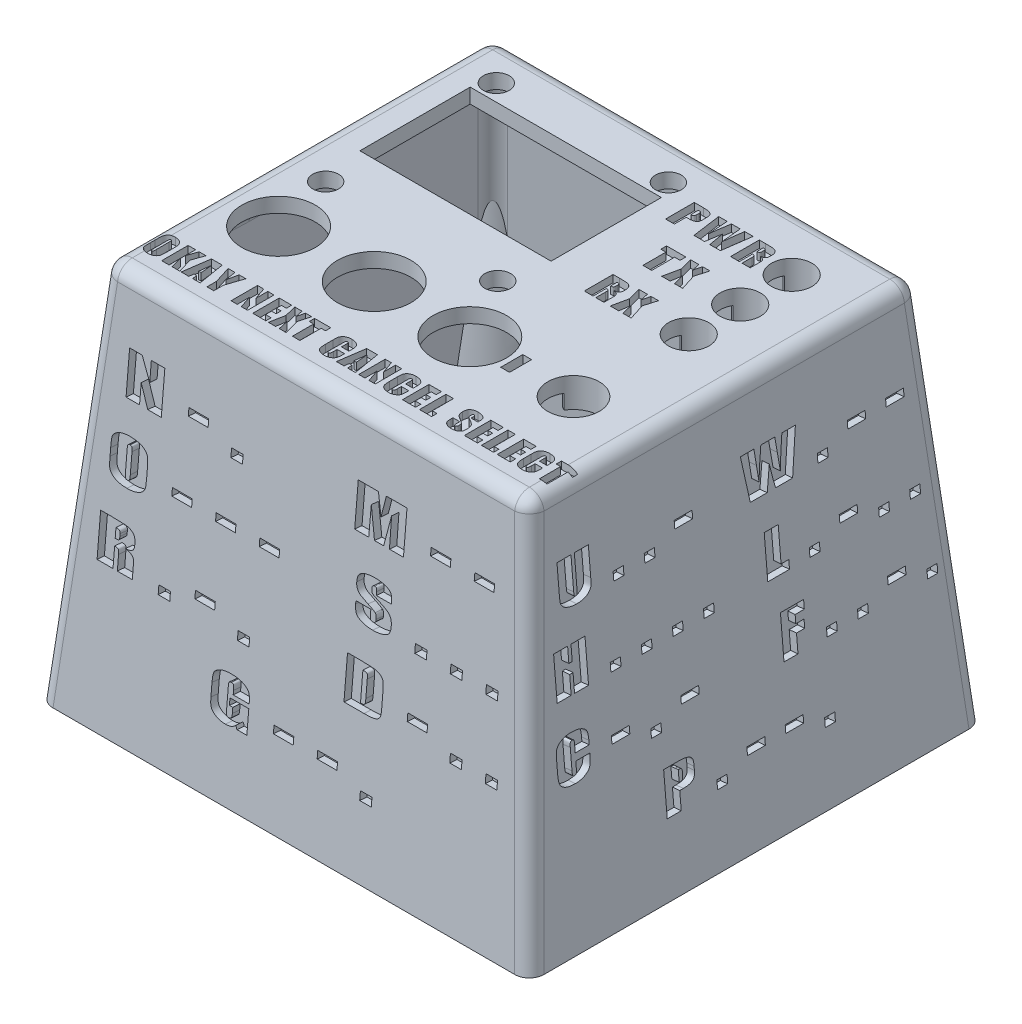
SolidWorks part; units mm, degrees
ref_plane "Front Plane" through (0, 0, 0) normal (0, 0, 1) x (1, 0, 0)
ref_plane "Top Plane" through (0, 0, 0) normal (0, 1, 0) x (1, 0, 0)
ref_plane "Right Plane" through (0, 0, 0) normal (1, 0, 0) x (0, 0, -1)
sketch "Sketch9" plane through (0, 0, 0) normal (0, 1, 0) x (1, 0, 0)
  line L1 (-27, 24.5) -> (27, 24.5)
  line L2 (-27, 24.5) -> (-27, -24.5)
  line L3 (-27, -24.5) -> (27, -24.5)
  line L4 (27, 24.5) -> (27, -24.5)
  line L5 (-27, 24.5) -> (27, -24.5) construction
  line L6 (-27, -24.5) -> (27, 24.5) construction
  point P0 (0, 0)
  dimension "D1" = 49
  dimension "D2" = 54
extrude "Boss-Extrude1" add sketch "Sketch9" against normal blind 50 draft 5 draft outward yes
shell "Shell3" thickness 2 removed face at (0, -50, 0) outward yes
sketch "Sketch11" plane through (0, 2, 0) normal (0, 1, 0) x (1, 0, 0)
  line L0 (-26.825, 26.3327) -> (-26.825, -26.3327) construction
  line L1 (28.8327, 26.3327) -> (-28.8327, 26.3327) construction
  line L6 (28.8327, -26.3327) -> (28.8327, 26.3327) construction
  line L7 (0, -26.3327) -> (0, 26.3327) construction
  line L8 (-28.8327, -26.3327) -> (28.8327, -26.3327) construction
  line L9 (28.8327, 26.3327) -> (-28.8327, 26.3327) construction
  line L17 (-11.1327, 18.5827) -> (-11.1327, 3.5827) construction
  line L18 (-24.1327, 3.5827) -> (1.8673, 3.5827)
  line L19 (-24.1327, 3.5827) -> (-24.1327, 18.5827)
  line L20 (-24.1327, 18.5827) -> (1.8673, 18.5827)
  line L21 (1.8673, 3.5827) -> (1.8673, 18.5827)
  line L22 (1.8673, 11.0827) -> (-24.1327, 11.0827) construction
  line L24 (-22.0027, 5.6527) -> (-0.2627, 5.6527) construction
  line L25 (-22.0027, 5.6527) -> (-22.0027, 16.5127) construction
  line L26 (-22.0027, 16.5127) -> (-0.2627, 16.5127) construction
  line L27 (-0.2627, 5.6527) -> (-0.2627, 16.5127) construction
  line L28 (-22.0027, 5.6527) -> (-0.2627, 16.5127) construction
  line L29 (-22.0027, 16.5127) -> (-0.2627, 5.6527) construction
  line L30 (-26.825, 24.3327) -> (26.8327, 24.3327) construction
  line L31 (-26.825, 24.3327) -> (-26.825, -24.3327) construction
  line L32 (-26.825, -24.3327) -> (26.8327, -24.3327) construction
  line L33 (26.8327, 24.3327) -> (26.8327, -24.3327) construction
  line L36 (-28.8327, 26.3327) -> (-28.8327, -26.3327) construction
  circle A0 centre (-22.8327, 20.8327) radius 1.75
  circle A1 centre (-22.8327, -2.3673) radius 1.75
  circle A2 centre (0.5673, -2.3673) radius 1.75
  circle A3 centre (0.5673, 20.8327) radius 1.75
  point P12 (0, 0)
  point P13 (0, 0)
  point P14 (-11.1327, 11.0827)
  point P27 (-11.1327, 11.0827)
  point P44 (-22.8327, 20.8327)
  dimension "D10" = 3.5
  dimension "D11" = 3.5
  dimension "D1" = 26
  dimension "D2" = 15
  dimension "D3" = 10.86
  dimension "D4" = 21.74
  dimension "D8" = 23.4
  dimension "D9" = 23.4
  dimension "D12" = 23.2
  dimension "D13" = 2.25
  dimension "D14" = 2
  dimension "D15" = 2
  dimension "D16" = 6
  dimension "D17" = 0
  dimension "D18" = 2
  dimension "D19" = 3.5
extrude "Cut-Extrude1" cut sketch "Sketch11" against normal up to surface (2 mm away) contours L19 L18 L21 L20 | A0 | A3 | A2 | A1 up to face at (0, 0, 0)
sketch "Sketch12" plane through (0, 2, 0) normal (0, 1, 0) x (1, 0, 0)
  line L0 (-26.825, -10.8327) -> (28.8327, -10.8327) construction
  line L1 (-26.825, 26.3327) -> (-26.825, -26.3327) construction
  line L2 (28.8327, -26.3327) -> (28.8327, 26.3327) construction
  line L4 (-26.8327, 26.3327) -> (-26.8327, -26.3327) construction
  line L5 (28.8327, 26.3327) -> (-28.8327, 26.3327) construction
  line L6 (-28.8327, -26.3327) -> (28.8327, -26.3327) construction
  line L7 (26.8327, 26.3327) -> (26.8327, -26.3327) construction
  line L8 (-26.8327, 24.3327) -> (26.8327, 24.3327) construction
  line L9 (-26.8327, -24.3327) -> (26.8327, -24.3327) construction
  line L10 (-28.8327, 26.3327) -> (-28.8327, -26.3327) construction
  line L15 (10.9327, -12.3327) -> (12.1327, -12.3327)
  line L16 (10.9327, -12.3327) -> (10.9327, -9.3327)
  line L17 (10.9327, -9.3327) -> (12.1327, -9.3327)
  line L18 (12.1327, -12.3327) -> (12.1327, -9.3327)
  line L19 (10.9327, -12.3327) -> (12.1327, -9.3327) construction
  line L20 (10.9327, -9.3327) -> (12.1327, -12.3327) construction
  circle A0 centre (-20.7673, -10.8327) radius 5
  circle A1 centre (-7.7673, -10.8327) radius 5
  circle A2 centre (5.2327, -10.8327) radius 5
  circle A4 centre (19.3327, -10.8327) radius 3.5
  circle A5 centre (19.3327, -10.8327) radius 7.5 construction
  point P7 (11.5327, -10.8327)
  dimension "D2" = 10
  dimension "D7" = 10
  dimension "D8" = 10
  dimension "D9" = 2
  dimension "D11" = 2
  dimension "D13" = 7
  dimension "D17" = 15
  dimension "D3" = 21.6
  dimension "D4" = 13
  dimension "D5" = 13
  dimension "D6" = 2
  dimension "D10" = 6.0577
  dimension "D12" = 2
  dimension "D14" = 13.5
  dimension "D15" = 7.5
  dimension "D16" = 13.5
  dimension "D18" = 1.2
  dimension "D19" = 3
  dimension "D20" = 7.8
extrude "Cut-Extrude3" cut sketch "Sketch12" against normal up to surface (2 mm away) up to face at (-22.8327, 0, 4.1173)
sketch "Sketch13" plane through (0, 2, 0) normal (0, 1, 0) x (1, 0, 0)
  line L0 (28.8327, -26.3327) -> (28.8327, 26.3327) construction
  line L2 (28.8327, 26.3327) -> (-28.8327, 26.3327) construction
  circle A4 centre (19.8327, 18.3327) radius 2.75
  circle A12 centre (19.8327, 11.3327) radius 2.75
  circle A13 centre (19.8327, 4.3327) radius 2.75
  dimension "D1" = 3
  dimension "D2" = 9
  dimension "D3" = 8
  dimension "D4" = 7
extrude "Cut-Extrude5" cut sketch "Sketch13" against normal up to surface (2 mm away) up to face at (-20.7673, 0, 15.8327)
sketch "Sketch14" plane through (0, 0, 0) normal (0, -1, 0) x (1, 0, 0)
  line L0 (22.5827, -18.3327) -> (19.8327, -18.3327) construction
  line L1 (19.8327, -18.3327) -> (17.0827, -18.3327) construction
  line L19 (22.2142, -19.7077) -> (19.8327, -18.3327) construction
  line L51 (19.8327, -18.3327) -> (19.8327, -21.0827) construction
  line L52 (17.4511, -19.7077) -> (19.8327, -18.3327) construction
  line L53 (17.4511, -19.7077) -> (17.0181, -19.9577)
  line L54 (22.2142, -16.9577) -> (22.6472, -16.7077)
  line L55 (22.2142, -19.7077) -> (22.6472, -19.9577)
  line L56 (17.4511, -16.9577) -> (17.0181, -16.7077)
  line L57 (17.4511, -12.7077) -> (17.0181, -12.9577)
  line L58 (22.2142, -12.7077) -> (22.6472, -12.9577)
  line L59 (22.2142, -9.9577) -> (22.6472, -9.7077)
  line L60 (17.4511, -9.9577) -> (17.0181, -9.7077)
  line L61 (17.4511, -5.7077) -> (17.0181, -5.9577)
  line L62 (22.2142, -5.7077) -> (22.6472, -5.9577)
  line L63 (22.2142, -2.9577) -> (22.6472, -2.7077)
  line L64 (17.4511, -2.9577) -> (17.0181, -2.7077)
  arc A25 (22.2142, -19.7077) -> (17.4511, -19.7077) centre (19.8327, -18.3327) cw
  circle A45 centre (19.8327, -18.3327) radius 2.75 construction
  arc A46 (22.6472, -19.9577) -> (17.0181, -19.9577) centre (19.8327, -18.3327) cw
  arc A47 (22.2142, -16.9577) -> (17.4511, -16.9577) centre (19.8327, -18.3327) ccw
  arc A48 (22.6472, -16.7077) -> (17.0181, -16.7077) centre (19.8327, -18.3327) ccw
  arc A49 (22.6472, -12.9577) -> (17.0181, -12.9577) centre (19.8327, -11.3327) cw
  arc A50 (22.2142, -12.7077) -> (17.4511, -12.7077) centre (19.8327, -11.3327) cw
  arc A51 (22.6472, -9.7077) -> (17.0181, -9.7077) centre (19.8327, -11.3327) ccw
  arc A52 (22.2142, -9.9577) -> (17.4511, -9.9577) centre (19.8327, -11.3327) ccw
  arc A53 (22.6472, -5.9577) -> (17.0181, -5.9577) centre (19.8327, -4.3327) cw
  arc A54 (22.2142, -5.7077) -> (17.4511, -5.7077) centre (19.8327, -4.3327) cw
  arc A55 (22.6472, -2.7077) -> (17.0181, -2.7077) centre (19.8327, -4.3327) ccw
  arc A56 (22.2142, -2.9577) -> (17.4511, -2.9577) centre (19.8327, -4.3327) ccw
  dimension "D1" = 30
  dimension "D2" = 0.5
  dimension "D3" = 3
  dimension "D4" = 7
extrude "Boss-Extrude2" add sketch "Sketch14" along normal blind 4 contours L57 A49 L58 A50 | A46 L53 A25 L55 | L54 A48 L56 A47 | L59 A51 L60 A52 | L61 A53 L62 A54 | L63 A55 L64 A56
sketch "Sketch19" plane through (0, 2, 0) normal (0, 1, 0) x (1, 0, 0)
  line L2 (-27.8327, 26.3327) -> (-27.8327, -26.3327) construction
  line L7 (28.8327, 26.3327) -> (-28.8327, 26.3327) construction
  line L8 (-28.8327, -26.3327) -> (28.8327, -26.3327) construction
  line L9 (-27.8327, -22.8327) -> (27.8327, -22.8327) construction
  line L10 (27.8327, 26.3327) -> (27.8327, -26.3327) construction
  line L11 (-28.8327, 26.3327) -> (-28.8327, -26.3327) construction
  line L12 (28.8327, -26.3327) -> (28.8327, 26.3327) construction
  text T0 "OKAY NEXT CANCEL SELECT" font "Impact" height 3.6
  dimension "D2" = 1
  dimension "D3" = 3.5
  dimension "D1" = 1
sketch "Sketch20" plane through (0, 2, 0) normal (0, 1, 0) x (1, 0, 0)
  line L3 (19.8327, 18.3327) -> (17.0827, 18.3327) construction
  line L4 (19.8327, 18.3327) -> (19.8327, 11.3327) construction
  line L5 (19.8327, 11.3327) -> (19.8327, 4.3327) construction
  line L6 (3.8327, 26.3327) -> (3.8327, -26.3327) construction
  line L7 (28.8327, 26.3327) -> (-28.8327, 26.3327) construction
  line L8 (-28.8327, -26.3327) -> (28.8327, -26.3327) construction
  line L9 (28.8327, -26.3327) -> (28.8327, 26.3327) construction
  line L10 (17.0827, 18.3327) -> (17.0827, 11.3327) construction
  line L11 (17.0827, 11.3327) -> (17.0827, 4.3327) construction
  line L12 (19.8327, 4.3327) -> (19.8327, 1.5827) construction
  line L13 (19.8327, 1.5827) -> (17.0827, 1.5827) construction
  line L14 (17.0827, 1.5827) -> (17.0827, 4.3327) construction
  line L15 (3.8327, 16.3327) -> (17.0827, 16.3327) construction
  line L16 (17.0827, 9.3327) -> (3.8327, 9.3327) construction
  line L17 (17.0827, 2.3327) -> (3.8327, 2.3327) construction
  circle A0 centre (19.8327, 18.3327) radius 2.75 construction
  circle A1 centre (19.8327, 11.3327) radius 2.75 construction
  circle A3 centre (19.8327, 4.3327) radius 2.75 construction
  text T0 "PWR" font "Impact" height in points 14
  text T1 "TX  " font "Impact" height in points 14
  text T2 "RX  " font "Impact" height in points 14
  dimension "D1" = 25
  dimension "D2" = 2
  dimension "D3" = 2
  dimension "D4" = 2
sketch "Sketch23" plane through (-28.7873, 2.5186, 0) normal (-0.9962, 0.0872, 0) x (0, 0, 1)
  line L0 (-29.8624, -41.0192) -> (29.8624, -41.0192) construction
  line L1 (-30.8821, -52.7192) -> (-26.3327, -0.5205) construction
  line L2 (30.8821, -52.7192) -> (26.3327, -0.5205) construction
  line L3 (-30.8821, -52.7192) -> (30.8821, -52.7192) construction
  line L4 (-28.9036, -30.0192) -> (28.9036, -30.0192) construction
  line L5 (22.0021, -41.0192) -> (22.0021, -30.0192) construction
  line L10 (-30.8821, -52.7192) -> (-30.8821, -30.0192) construction
  line L11 (30.8821, -52.7192) -> (30.8821, -30.0192) construction
  line L16 (-22.0021, -41.0192) -> (-22.0021, -30.0192) construction
  line L17 (13.0021, -41.0192) -> (13.0021, -30.0192) construction
  line L18 (-13.0021, -41.0192) -> (-0.5021, -41.0192)
  line L19 (-13.0021, -41.0192) -> (-13.0021, -30.0192)
  line L20 (-13.0021, -30.0192) -> (-0.5021, -30.0192)
  line L21 (-0.5021, -41.0192) -> (-0.5021, -30.0192)
  circle A0 centre (7.0021, -38.5192) radius 3.25
  dimension "D8" = 6.5
  dimension "D1" = 11.7
  dimension "D2" = 11
  dimension "D3" = 8.88
  dimension "D4" = 8.88
  dimension "D5" = 9
  dimension "D6" = 12.5
  dimension "D7" = 9
  dimension "D9" = 6
  dimension "D10" = 2.5
extrude "Cut-Extrude6" cut sketch "Sketch23" against normal blind 3
fillet "Fillet1" radius 2 16 edges at (-27, 0, 0) (0, 0, -24.5) (27, 0, 0) (0, 0, 24.5) (-29.1872, -25, 26.6872) (29.1872, -25, 26.6872) (29.1872, -25, -26.6872) (-29.1872, -25, -26.6872) (31.1074, -24, -28.6074) (31.1074, -24, 28.6074) (-31.1074, -24, 28.6074) (-31.1074, -24, -28.6074) (0, 2, -26.3327) (-28.8327, 2, 0) (0, 2, 26.3327) (28.8327, 2, 0)
sketch "Sketch24" plane through (0, -50, 0) normal (0, -1, 0) x (1, 0, 0)
  line L0 (29.382, -28.8744) -> (33.3821, -28.8744) construction
  line L1 (29.382, -28.8744) -> (-29.382, -28.8744) construction
  line L2 (33.3821, 28.8897) -> (33.3821, -28.8897) construction
  line L3 (29.382, -28.8744) -> (25.1673, -24.6597) construction
  line L4 (31.3744, -26.882) -> (31.3897, -30.8821) construction
  line L5 (31.3744, 26.882) -> (31.3744, -26.882) construction
  line L6 (31.3744, -21.8744) -> (31.3744, -26.882)
  line L7 (24.3821, -28.8744) -> (29.382, -28.8744)
  line L8 (0, -30.8821) -> (0, 30.8821) construction
  line L9 (31.3897, -30.8821) -> (-31.3897, -30.8821) construction
  line L10 (-31.3897, 30.8821) -> (31.3897, 30.8821) construction
  line L11 (33.3821, 0) -> (-33.3821, 0) construction
  line L12 (-33.3821, -28.8897) -> (-33.3821, 28.8897) construction
  line L13 (-31.3744, -21.8744) -> (-31.3744, -26.882)
  line L14 (-24.3821, -28.8744) -> (-29.382, -28.8744)
  line L15 (-24.3821, 28.8744) -> (-29.382, 28.8744)
  line L16 (-31.3744, 21.8744) -> (-31.3744, 26.882)
  line L17 (31.3744, 21.8744) -> (31.3744, 26.882)
  line L18 (24.3821, 28.8744) -> (29.382, 28.8744)
  arc A2 (24.3821, -28.8744) -> (31.3744, -21.8744) centre (31.3821, -28.8744) cw
  arc A3 (31.3744, -26.882) -> (29.382, -28.8744) centre (29.382, -26.882) cw
  arc A4 (-24.3821, -28.8744) -> (-31.3744, -21.8744) centre (-31.3821, -28.8744) ccw
  arc A5 (-31.3744, -26.882) -> (-29.382, -28.8744) centre (-29.382, -26.882) ccw
  arc A6 (-24.3821, 28.8744) -> (-31.3744, 21.8744) centre (-31.3821, 28.8744) cw
  arc A7 (-31.3744, 26.882) -> (-29.382, 28.8744) centre (-29.382, 26.882) cw
  arc A8 (24.3821, 28.8744) -> (31.3744, 21.8744) centre (31.3821, 28.8744) ccw
  arc A9 (31.3744, 26.882) -> (29.382, 28.8744) centre (29.382, 26.882) ccw
  dimension "D1" = 7
extrude "Boss-Extrude5" add sketch "Sketch24" against normal blind 40 draft 3.5
sketch "Sketch25" plane through (0, -50, 0) normal (0, -1, 0) x (1, 0, 0)
  line L0 (31.3744, -21.8744) -> (31.3897, -30.8821) construction
  line L1 (24.3821, -28.8744) -> (33.3821, -28.8897) construction
  line L2 (0, -30.8821) -> (0, 30.8821) construction
  line L3 (31.3897, -30.8821) -> (-31.3897, -30.8821) construction
  line L4 (-31.3897, 30.8821) -> (31.3897, 30.8821) construction
  line L5 (33.3821, 0) -> (-33.3821, 0) construction
  line L6 (33.3821, 28.8897) -> (33.3821, -28.8897) construction
  line L7 (-33.3821, -28.8897) -> (-33.3821, 28.8897) construction
  circle A0 centre (28.8821, -26.3821) radius 2.125
  circle A1 centre (-28.8821, -26.3821) radius 2.125
  circle A2 centre (-28.8821, 26.3821) radius 2.125
  circle A3 centre (28.8821, 26.3821) radius 2.125
  dimension "D1" = 4.25
  dimension "D2" = 2.5
  dimension "D3" = 2.5
extrude "Cut-Extrude7" cut sketch "Sketch25" against normal blind 15 draft 1.5
extrude "Cut-Extrude8" cut sketch "Sketch19" against normal blind 1
extrude "Cut-Extrude9" cut sketch "Sketch20" against normal blind 1
sketch "Sketch27" plane through (0, 0, 0) normal (0, -1, 0) x (1, 0, 0)
  line L0 (15.8327, 10.8327) -> (22.8327, 10.8327) construction
  line L1 (19.3327, 7.3327) -> (19.3327, 14.3327) construction
  line L2 (19.3327, 10.8327) -> (22.3638, 9.0827) construction
  line L3 (19.3327, 10.8327) -> (16.3016, 9.0827) construction
  line L4 (22.3638, 9.0827) -> (22.7968, 8.8327)
  line L5 (16.3016, 9.0827) -> (15.8686, 8.8327)
  line L6 (16.3016, 12.5827) -> (15.8686, 12.8327)
  line L7 (22.3638, 12.5827) -> (22.7968, 12.8327)
  circle A0 centre (19.3327, 10.8327) radius 3.5 construction
  arc A1 (22.7968, 8.8327) -> (15.8686, 8.8327) centre (19.3327, 10.8327) cw
  arc A2 (16.3016, 9.0827) -> (22.3638, 9.0827) centre (19.3327, 10.8327) ccw
  arc A3 (22.7968, 12.8327) -> (15.8686, 12.8327) centre (19.3327, 10.8327) ccw
  arc A4 (16.3016, 12.5827) -> (22.3638, 12.5827) centre (19.3327, 10.8327) cw
  dimension "D1" = 30
  dimension "D2" = 0.5
extrude "Boss-Extrude6" add sketch "Sketch27" along normal blind 2
sketch "Sketch28" plane through (-28.7873, 2.5186, 0) normal (-0.9962, 0.0872, 0) x (0, 0, 1)
  line L0 (-24.5, -2.3532) -> (-24.5, -52.7192) construction
  line L1 (-28.8897, -52.7192) -> (28.8897, -52.7192) construction
  line L2 (24.5, -2.3532) -> (24.5, -52.7192) construction
  line L3 (-24.5, -14.3532) -> (24.5, -14.3532) construction
  line L5 (24.5, -2.3532) -> (-24.5, -2.3532) construction
  text T0 "E .       T -\r\nI . .     A . -" font "Impact" height in points 20
  dimension "D1" = 12
extrude "Cut-Extrude11" cut sketch "Sketch28" against normal blind 1
sketch "Sketch29" plane through (0, 2.3015, 26.3063) normal (0, 0.0872, 0.9962) x (1, 0, 0)
  line L0 (-28.0459, -14.1353) -> (28.0459, -14.1353) construction
  line L1 (-27, -2.1353) -> (-31.3897, -52.5013) construction
  line L2 (31.3897, -52.5013) -> (27, -2.1353) construction
  line L3 (27, -2.1353) -> (-27, -2.1353) construction
  text T0 "N - .      M - -\r\nO - - -    S . . .\r\nR . - .     D - . .\r\nG - - ." font "Impact" height in points 20
  dimension "D1" = 12
extrude "Cut-Extrude12" cut sketch "Sketch29" against normal blind 1
sketch "Sketch30" plane through (28.7873, 2.5186, 0) normal (0.9962, 0.0872, 0) x (0, 0, -1)
  line L0 (-25.5459, -14.3532) -> (25.5459, -14.3532) construction
  line L1 (-24.5, -2.3532) -> (-28.8897, -52.7192) construction
  line L2 (28.8897, -52.7192) -> (24.5, -2.3532) construction
  line L3 (24.5, -2.3532) -> (-24.5, -2.3532) construction
  text T0 "U . . -   W . - -\r\nH . . . .   L . - . .\r\nC - . -     F . . - .\r\nP . - - ." font "Impact" height in points 20
  dimension "D1" = 12
extrude "Cut-Extrude13" cut sketch "Sketch30" against normal blind 1
sketch "Sketch31" plane through (0, 2.3015, -26.3063) normal (0, 0.0872, -0.9962) x (-1, 0, 0)
  line L0 (-28.0459, -14.1353) -> (28.0459, -14.1353) construction
  line L1 (-27, -2.1353) -> (-31.3897, -52.5013) construction
  line L2 (31.3897, -52.5013) -> (27, -2.1353) construction
  line L3 (27, -2.1353) -> (-27, -2.1353) construction
  text T0 "B - . . .    K - . -\r\nY - . - -   V . . . -\r\nJ . - - -    X - . . -\r\nQ - - . -    Z - - . ." font "Impact" height in points 20
  dimension "D1" = 12
extrude "Cut-Extrude14" cut sketch "Sketch31" against normal blind 1
